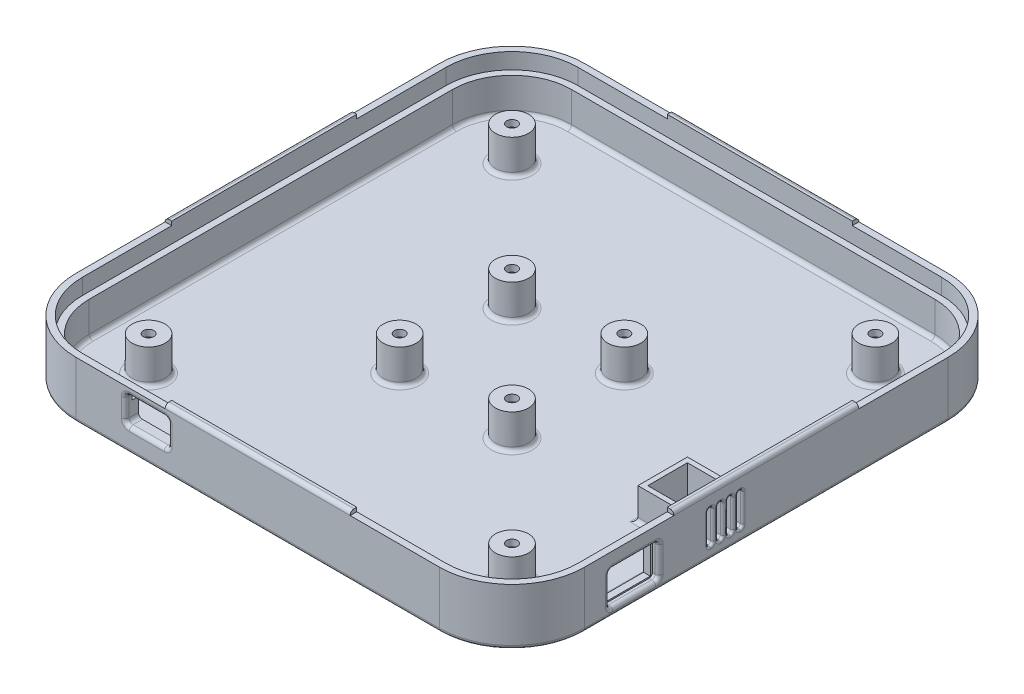
SolidWorks part; units mm, degrees
ref_plane "Front Plane" through (0, 0, 0) normal (0, 0, 1) x (1, 0, 0)
ref_plane "Top Plane" through (0, 0, 0) normal (0, 1, 0) x (1, 0, 0)
ref_plane "Right Plane" through (0, 0, 0) normal (1, 0, 0) x (0, 0, -1)
sketch "Sketch1" plane through (0, 0, 0) normal (0, 1, 0) x (1, 0, 0)
  line L0 (0, 75) -> (55, 75)
  line L1 (75, 55) -> (75, 0)
  line L2 (75, 0) -> (75, -55)
  line L3 (55, -75) -> (0, -75)
  line L4 (0, -75) -> (-55, -75)
  line L5 (-75, -55) -> (-75, 0)
  line L6 (-75, 0) -> (-75, 55)
  line L7 (-55, 75) -> (0, 75)
  line L8 (-55, 77) -> (0, 77)
  line L9 (0, 77) -> (55, 77)
  line L10 (77, 55) -> (77, 0)
  line L11 (77, 0) -> (77, -55)
  line L12 (55, -77) -> (0, -77)
  line L13 (0, -77) -> (-55, -77)
  line L14 (-77, -55) -> (-77, 0)
  line L15 (-77, 0) -> (-77, 55)
  arc A0 (55, 75) -> (75, 55) centre (55, 55) cw
  arc A1 (75, -55) -> (55, -75) centre (55, -55) cw
  arc A2 (-55, -75) -> (-75, -55) centre (-55, -55) cw
  arc A3 (-75, 55) -> (-55, 75) centre (-55, 55) cw
  arc A4 (55, 77) -> (77, 55) centre (55, 55) cw
  arc A5 (77, -55) -> (55, -77) centre (55, -55) cw
  arc A6 (-55, -77) -> (-77, -55) centre (-55, -55) cw
  arc A7 (-77, 55) -> (-55, 77) centre (-55, 55) cw
  point P24 (0, 0)
  dimension "D1" = 75
  dimension "D2" = 75
  dimension "D3" = 20
  dimension "D5" = 2
  dimension "D4" = 4
extrude "Boss-Extrude2" add sketch "Sketch1" along normal blind 15.2
sketch "Sketch4" plane through (0, 0, 0) normal (0, 1, 0) x (1, 0, 0)
  line L20 (55, 73) -> (-55, 73)
  line L21 (73, -55) -> (73, 55)
  line L22 (-55, -73) -> (55, -73)
  line L23 (-73, 55) -> (-73, -55)
  line L24 (55, 73) -> (-55, 73)
  line L25 (73, -55) -> (73, 55)
  line L26 (-55, -73) -> (55, -73)
  line L27 (-73, 55) -> (-73, -55)
  line L44 (55, 75) -> (-55, 75)
  line L45 (75, -55) -> (75, 55)
  line L46 (-55, -75) -> (55, -75)
  line L47 (-75, 55) -> (-75, -55)
  line L48 (55, 75) -> (-55, 75)
  line L49 (75, -55) -> (75, 55)
  line L50 (-55, -75) -> (55, -75)
  line L51 (-75, 55) -> (-75, -55)
  arc A24 (73, 55) -> (55, 73) centre (55, 55) ccw
  arc A25 (55, -73) -> (73, -55) centre (55, -55) ccw
  arc A26 (-73, -55) -> (-55, -73) centre (-55, -55) ccw
  arc A27 (-55, 73) -> (-73, 55) centre (-55, 55) ccw
  arc A28 (73, 55) -> (55, 73) centre (55, 55) ccw
  arc A29 (55, -73) -> (73, -55) centre (55, -55) ccw
  arc A30 (-73, -55) -> (-55, -73) centre (-55, -55) ccw
  arc A31 (-55, 73) -> (-73, 55) centre (-55, 55) ccw
  arc A52 (75, 55) -> (55, 75) centre (55, 55) ccw
  arc A53 (55, -75) -> (75, -55) centre (55, -55) ccw
  arc A54 (-75, -55) -> (-55, -75) centre (-55, -55) ccw
  arc A55 (-55, 75) -> (-75, 55) centre (-55, 55) ccw
  arc A56 (75, 55) -> (55, 75) centre (55, 55) ccw
  arc A57 (55, -75) -> (75, -55) centre (55, -55) ccw
  arc A58 (-75, -55) -> (-55, -75) centre (-55, -55) ccw
  arc A59 (-55, 75) -> (-75, 55) centre (-55, 55) ccw
  dimension "D1" = 2
  dimension "D2" = 0
extrude "Boss-Extrude3" add sketch "Sketch4" along normal blind 10.4
sketch "Sketch5" plane through (0, 0, 0) normal (0, -1, 0) x (1, 0, 0)
  line L8 (-55, -77) -> (55, -77)
  line L9 (77, -55) -> (77, 55)
  line L10 (55, 77) -> (-55, 77)
  line L11 (-77, 55) -> (-77, -55)
  line L12 (-55, -77) -> (55, -77)
  line L13 (77, -55) -> (77, 55)
  line L14 (55, 77) -> (-55, 77)
  line L15 (-77, 55) -> (-77, -55)
  arc A8 (-77, -55) -> (-55, -77) centre (-55, -55) ccw
  arc A9 (55, -77) -> (77, -55) centre (55, -55) ccw
  arc A10 (77, 55) -> (55, 77) centre (55, 55) ccw
  arc A11 (-55, 77) -> (-77, 55) centre (-55, 55) ccw
  arc A12 (-77, -55) -> (-55, -77) centre (-55, -55) ccw
  arc A13 (55, -77) -> (77, -55) centre (55, -55) ccw
  arc A14 (77, 55) -> (55, 77) centre (55, 55) ccw
  arc A15 (-55, 77) -> (-77, 55) centre (-55, 55) ccw
  dimension "D1" = 0
extrude "Boss-Extrude4" add sketch "Sketch5" along normal blind 2
sketch "Sketch6" plane through (0, 0, 77) normal (0, 0, 1) x (1, 0, 0)
  line L0 (-77, 15.2) -> (-77, -2) construction
  line L1 (-40.075, 5) -> (-27.075, 5)
  line L2 (-40.075, 5) -> (-40.075, 13)
  line L3 (-40.075, 13) -> (-27.075, 13)
  line L4 (-27.075, 5) -> (-27.075, 13)
  line L5 (-40.075, 5) -> (-27.075, 13) construction
  line L6 (-40.075, 13) -> (-27.075, 5) construction
  line L7 (55, -2) -> (-55, -2) construction
  point P0 (-33.575, 9)
  dimension "D1" = 13
  dimension "D2" = 43.425
  dimension "D3" = 11
  dimension "D4" = 8
extrude "Cut-Extrude1" cut sketch "Sketch6" against normal up to next
sketch "Sketch7" plane through (77, 0, 0) normal (1, 0, 0) x (0, 0, -1)
  line L0 (-13.15, 11.6) -> (-13.15, 1.6)
  line L1 (-17.65, 11.6) -> (-16.15, 11.6)
  line L2 (-17.65, 11.6) -> (-17.65, 1.6)
  line L3 (-17.65, 1.6) -> (-16.15, 1.6)
  line L4 (-16.15, 11.6) -> (-16.15, 1.6)
  line L5 (-14.65, 11.6) -> (-13.15, 11.6)
  line L6 (-14.65, 11.6) -> (-14.65, 1.6)
  line L7 (-14.65, 1.6) -> (-13.15, 1.6)
  line L8 (-10.15, 11.6) -> (-10.15, 1.6)
  line L9 (-11.65, 11.6) -> (-10.15, 11.6)
  line L10 (-11.65, 11.6) -> (-11.65, 1.6)
  line L11 (-11.65, 1.6) -> (-10.15, 1.6)
  line L12 (-7.15, 11.6) -> (-7.15, 1.6)
  line L13 (-8.65, 11.6) -> (-7.15, 11.6)
  line L14 (-8.65, 11.6) -> (-8.65, 1.6)
  line L15 (-8.65, 1.6) -> (-7.15, 1.6)
  line L16 (-13.15, 6.6) -> (-11.65, 6.6) construction
  line L17 (-14.65, 6.6) -> (-16.15, 6.6) construction
  line L18 (-10.15, 6.6) -> (-8.65, 6.6) construction
  line L19 (-77, 15.2) -> (-77, -2) construction
  line L21 (-55, 6.6) -> (55, 6.6) construction
  line L22 (-55, 15.2) -> (-55, -2) construction
  line L23 (55, 15.2) -> (55, -2) construction
  point P22 (-12.4, 6.6)
  dimension "D1" = 1.5
  dimension "D3" = 64.6
  dimension "D4" = 1.5
  dimension "D5" = 10
  dimension "D2" = 4
extrude "Cut-Extrude2" cut sketch "Sketch7" against normal up to next
fillet "Fillet4" radius 1.2 8 edges at (70.5563, -2, 70.5563) (77, -2, 0) (70.5563, -2, -70.5563) (0, -2, -77) (-70.5563, -2, -70.5563) (-77, -2, 0) (-70.5563, -2, 70.5563) (0, -2, 77)
sketch "Sketch10" plane through (0, 0, 0) normal (0, 1, 0) x (1, 0, 0)
  line L0 (73, -55) -> (73, 55) construction
  line L1 (73, -4.9) -> (58, -4.9)
  line L2 (73, -4.9) -> (73, -6.4)
  line L3 (73, -19.9) -> (58, -19.9)
  line L4 (58, -4.9) -> (58, -19.9)
  line L5 (-55, -77) -> (55, -77) construction
  line L6 (73, -18.4) -> (73, -19.9)
  line L7 (73, -6.4) -> (59.5, -6.4)
  line L9 (73, -18.4) -> (59.5, -18.4)
  line L10 (59.5, -6.4) -> (59.5, -18.4)
  point P7 (58, -12.4)
  dimension "D1" = 15
  dimension "D2" = 15
  dimension "D3" = 64.6
  dimension "D4" = 1.5
  dimension "D5" = 1.5
  dimension "D6" = 1.5
extrude "Boss-Extrude6" add sketch "Sketch10" along normal blind 9.5
sketch "Sketch14" plane through (0, -2, 0) normal (0, -1, 0) x (1, 0, 0)
  line L0 (-77, -55) -> (-77, 55) construction
  line L1 (-55, 77) -> (55, 77) construction
  line L2 (-75.8, 0) -> (75.8, 0) construction
  line L3 (-75.8, 55) -> (-75.8, -55) construction
  line L4 (75.8, -55) -> (75.8, 55) construction
  circle A0 centre (-55, 55) radius 3
  circle A1 centre (-17, 17) radius 3
  dimension "D1" = 6
  dimension "D4" = 6
  dimension "D2" = 22
  dimension "D3" = 22
  dimension "D5" = 17
  dimension "D6" = 17
extrude "Cut-Extrude5" cut sketch "Sketch14" against normal offset from surface (10.4 mm away) 2 up to face at (-12.3763, 10.4, -6.4731)
sketch "Sketch15" plane through (0, 0, 0) normal (0, 1, 0) x (1, 0, 0)
  circle A0 centre (-55, -55) radius 3
  circle A1 centre (-55, -55) radius 5
  circle A2 centre (-17, -17) radius 3
  circle A3 centre (-17, -17) radius 5
  dimension "D1" = 2
  dimension "D2" = 2
extrude "Boss-Extrude8" add sketch "Sketch15" along normal offset from surface (8.4 mm away) 2 up to face at (-12.3763, 10.4, -6.4731)
sketch "Sketch16" plane through (0, 8.4, 0) normal (0, 1, 0) x (1, 0, 0)
  circle A0 centre (-55, -55) radius 5
  circle A1 centre (-55, -55) radius 1.6
  circle A3 centre (-17, -17) radius 1.6
  circle A4 centre (-17, -17) radius 5
  dimension "D1" = 3.2
  dimension "D2" = 3.2
extrude "Boss-Extrude9" add sketch "Sketch16" along normal up to surface (2 mm away) up to face at (-12.3763, 10.4, -6.4731)
mirror "Mirror1" about plane through (0, 0, 0) normal (0, 0, 1) of "Boss-Extrude8", "Boss-Extrude9", "Cut-Extrude5"
mirror "Mirror2" about plane through (0, 0, 0) normal (1, 0, 0) of "Mirror1"
sketch "Sketch17" plane through (0, 15.2, 0) normal (0, 1, 0) x (1, 0, 0)
  line L0 (-55, -75) -> (55, -75) construction
  line L1 (-28, -75) -> (28, -75)
  line L2 (-28, -75) -> (-28, -77)
  line L3 (-28, -77) -> (28, -77)
  line L4 (28, -75) -> (28, -77)
  line L5 (-55, -77) -> (55, -77) construction
  line L6 (77, -55) -> (77, 55) construction
  line L7 (77, 28) -> (75, 28)
  line L8 (77, 28) -> (77, -28)
  line L9 (77, -28) -> (75, -28)
  line L10 (75, 28) -> (75, -28)
  line L11 (75, -55) -> (75, 55) construction
  line L12 (55, 77) -> (-55, 77) construction
  line L13 (28, 77) -> (-28, 77)
  line L14 (28, 77) -> (28, 75)
  line L15 (28, 75) -> (-28, 75)
  line L16 (-28, 77) -> (-28, 75)
  line L17 (55, 75) -> (-55, 75) construction
  line L18 (-75, 55) -> (-75, -55) construction
  line L19 (-75, 28) -> (-77, 28)
  line L20 (-75, 28) -> (-75, -28)
  line L21 (-75, -28) -> (-77, -28)
  line L22 (-77, 28) -> (-77, -28)
  line L23 (-77, 55) -> (-77, -55) construction
  dimension "D1" = 27
  dimension "D2" = 27
  dimension "D3" = 27
  dimension "D4" = 27
  dimension "D5" = 27
  dimension "D6" = 27
  dimension "D7" = 27
  dimension "D8" = 27
extrude "Boss-Extrude10" add sketch "Sketch17" along normal blind 1.2
fillet "Fillet7" radius 1.2 4 edges at (0, 16.4, 77) (77, 16.4, 0) (0, 16.4, -77) (-77, 16.4, 0)
fillet "Fillet8" radius 1.2 8 edges at (-40.075, 9, 77) (-33.575, 5, 77) (-33.575, 13, 77) (-27.075, 9, 77) (-27.075, 13, 76) (-40.075, 13, 76) (-40.075, 5, 75) (-27.075, 5, 75)
fillet "Fillet9" radius 0.75 40 edges at (75, 11, 7.15) (75, 11, 8.65) (75, 11, 10.15) (75, 11, 11.65) (75, 11, 13.15) (75, 11, 14.65) (75, 11, 16.15) (75, 11, 17.65) (73, 6, 8.65) (73, 6, 7.15) (73, 6, 11.65) (73, 6, 10.15) (73, 6, 14.65) (73, 6, 13.15) (73, 6, 17.65) (73, 6, 16.15) (77, 6.6, 17.65) (76, 11.6, 8.65) (76, 11.6, 7.15) (76, 11.6, 11.65) (76, 11.6, 10.15) (76, 11.6, 14.65) (76, 11.6, 13.15) (76, 11.6, 17.65) (76, 11.6, 16.15) (75, 1.6, 7.15) (75, 1.6, 8.65) (75, 1.6, 10.15) (75, 1.6, 11.65) (75, 1.6, 13.15) (75, 1.6, 14.65) (75, 1.6, 16.15) (75, 1.6, 17.65) (77, 6.6, 8.65) (77, 6.6, 11.65) (77, 6.6, 14.65) (77, 6.6, 10.15) (77, 6.6, 13.15) (77, 6.6, 16.15) (77, 6.6, 7.15)
fillet "Fillet10" radius 1.2 20 edges at (17, 0, -22) (-17, 0, 12) (58, 0, 12.4) (65.5, 0, 19.9) (73, 0, 37.45) (67.7279, 0, 67.7279) (0, 0, 73) (-67.7279, 0, 67.7279) (-73, 0, 0) (-67.7279, 0, -67.7279) (0, 0, -73) (67.7279, 0, -67.7279) (73, 0, -25.05) (65.5, 0, 4.9) (-55, 0, 50) (-55, 0, -60) (-17, 0, -22) (55, 0, -60) (55, 0, 60) (17, 0, 22)
sketch "Sketch18" plane through (77, 0, 0) normal (1, 0, 0) x (0, 0, -1)
  line L0 (55, -2) -> (-55, -2) construction
  line L1 (-46.5, 0.5) -> (-33.5, 0.5)
  line L2 (-47.5, 1.5) -> (-47.5, 9.5)
  line L3 (-46.5, 10.5) -> (-33.5, 10.5)
  line L4 (-32.5, 1.5) -> (-32.5, 9.5)
  line L5 (-47.5, 0.5) -> (-32.5, 10.5) construction
  line L6 (-47.5, 10.5) -> (-32.5, 0.5) construction
  arc A0 (-33.5, 10.5) -> (-32.5, 9.5) centre (-33.5, 9.5) cw
  arc A1 (-33.5, 0.5) -> (-32.5, 1.5) centre (-33.5, 1.5) ccw
  arc A2 (-46.5, 0.5) -> (-47.5, 1.5) centre (-46.5, 1.5) cw
  arc A3 (-47.5, 9.5) -> (-46.5, 10.5) centre (-46.5, 9.5) cw
  point P0 (-40, 5.5)
  dimension "D3" = 1
  dimension "D1" = 15
  dimension "D2" = 10
  dimension "D4" = 7.5
  dimension "D5" = 37
extrude "Cut-Extrude6" cut sketch "Sketch18" against normal blind 2
sketch "Sketch19" plane through (75, 0, 0) normal (1, 0, 0) x (0, 0, -1)
  line L0 (55, -2) -> (-55, -2) construction
  line L1 (-46.85, 0.9) -> (-33.15, 0.9)
  line L2 (-46.85, 0.9) -> (-46.85, 10.1)
  line L3 (-46.85, 10.1) -> (-33.15, 10.1)
  line L4 (-33.15, 0.9) -> (-33.15, 10.1)
  line L5 (-46.85, 0.9) -> (-33.15, 10.1) construction
  line L6 (-46.85, 10.1) -> (-33.15, 0.9) construction
  line L7 (-77, 15.2) -> (-77, -0.8) construction
  point P0 (-40, 5.5)
  point P5 (-42.061, 5.9166)
  dimension "D1" = 13.7
  dimension "D2" = 9.2
  dimension "D3" = 7.5
  dimension "D4" = 37
extrude "Cut-Extrude7" cut sketch "Sketch19" against normal up to next
fillet "Fillet11" radius 1.2 8 edges at (77, 0.7929, 32.7929) (77, 0.7929, 47.2071) (77, 5.5, 47.5) (77, 10.2071, 47.2071) (77, 10.5, 40) (77, 10.2071, 32.7929) (77, 5.5, 32.5) (77, 0.5, 40)
